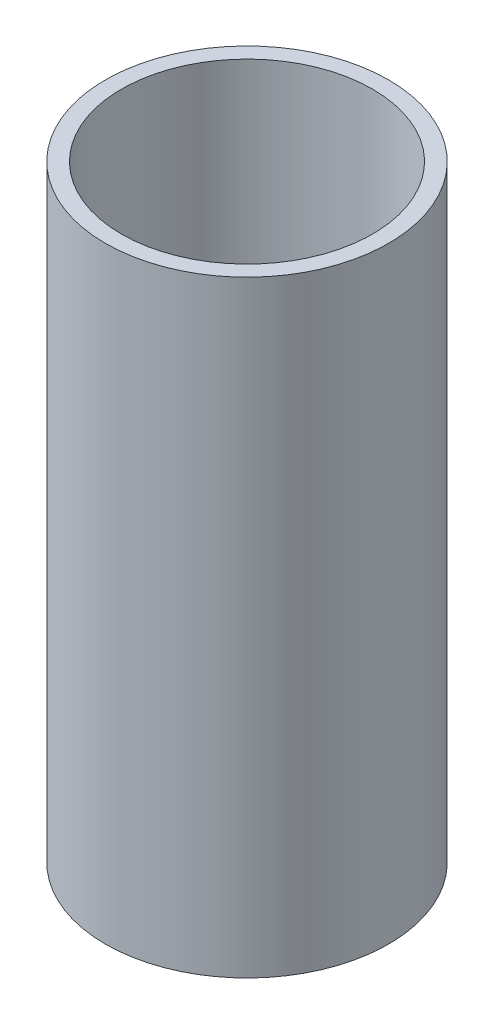
SolidWorks part; units mm, degrees
ref_plane "Front Plane" through (0, 0, 0) normal (0, 0, 1) x (1, 0, 0)
ref_plane "Top Plane" through (0, 0, 0) normal (0, 1, 0) x (1, 0, 0)
ref_plane "Right Plane" through (0, 0, 0) normal (1, 0, 0) x (0, 0, -1)
sketch "Sketch1" plane through (0, 0, 0) normal (0, 1, 0) x (1, 0, 0)
  circle A0 centre (0, 0) radius 60
  dimension "SLEEVE_OD" = 120
extrude "Boss-Extrude1" add sketch "Sketch1" along normal blind 257.1585
sketch "Sketch2" plane through (0, 0, 0) normal (0, 1, 0) x (1, 0, 0)
  circle A0 centre (0, 0) radius 53.2018
  dimension "BORE_D" = 106.4037
extrude "Cut-Extrude1" cut sketch "Sketch2" along normal through all
chamfer "Chamfer1" distance 3.9932 angle 53.343 rebuild error yes
